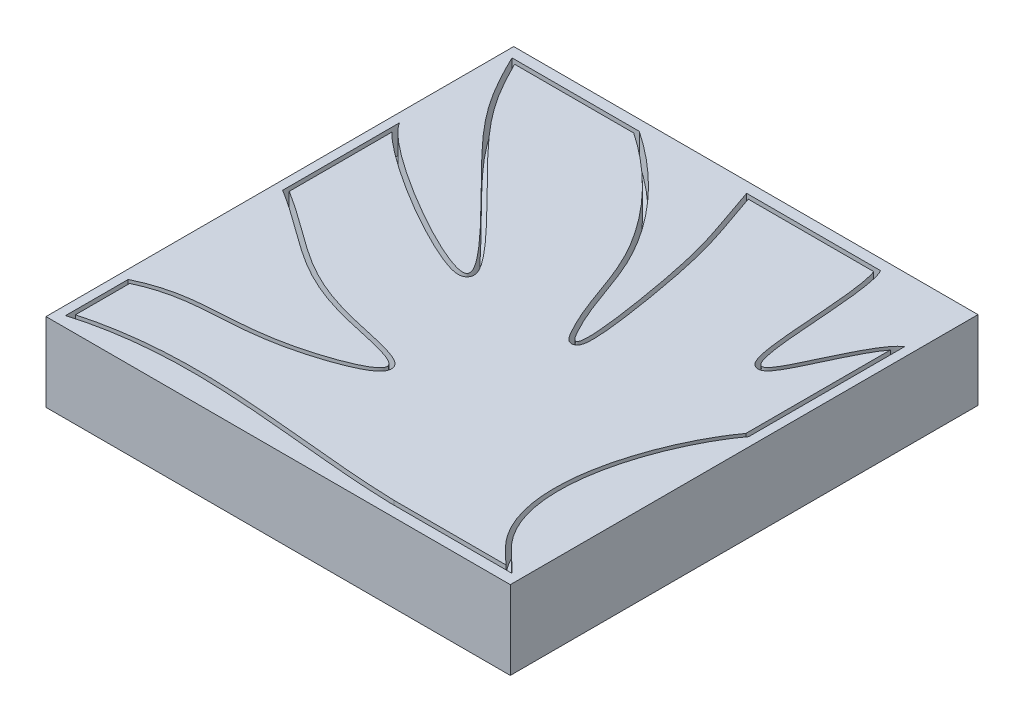
SolidWorks part; units mm, degrees
ref_plane "前视基准面" through (0, 0, 0) normal (0, 0, 1) x (1, 0, 0)
ref_plane "上视基准面" through (0, 0, 0) normal (0, 1, 0) x (1, 0, 0)
ref_plane "右视基准面" through (0, 0, 0) normal (1, 0, 0) x (0, 0, -1)
sketch "草图1" plane through (0, 0, 0) normal (0, 1, 0) x (1, 0, 0)
  circle A0 centre (0, 0) radius 18.7
  dimension "D1" = 37.4
extrude "凸台-拉伸1" add sketch "草图1" along normal blind 10
sketch "草图2" plane through (0, 10, 0) normal (0, 1, 0) x (1, 0, 0)
  line L1 (-10.5, -10.5) -> (10.5, -10.5)
  line L2 (-10.5, -10.5) -> (-10.5, 10.5)
  line L3 (-10.5, 10.5) -> (10.5, 10.5)
  line L4 (10.5, -10.5) -> (10.5, 10.5)
  line L5 (-10.5, -10.5) -> (10.5, 10.5) construction
  line L6 (-10.5, 10.5) -> (10.5, -10.5) construction
  point P0 (0, 0)
  dimension "D1" = 21
  dimension "D2" = 21
extrude "切除-拉伸1" cut sketch "草图2" against normal blind 3
sketch "草图3" plane through (0, 0, 0) normal (0, -1, 0) x (1, 0, 0)
  line L1 (-25, -25) -> (25, -25)
  line L2 (-25, -25) -> (-25, 25)
  line L3 (-25, 25) -> (25, 25)
  line L4 (25, -25) -> (25, 25)
  line L5 (-25, -25) -> (25, 25) construction
  line L6 (-25, 25) -> (25, -25) construction
  circle A0 centre (0, 0) radius 20
  point P0 (0, 0)
  circle M3 centre (0, 0) radius 18.7
  dimension "D3" = 40
  dimension "D1" = 50
  dimension "D2" = 50
extrude "凸台-拉伸2" add sketch "草图3" against normal blind 10 separate body
extrude "凸台-拉伸3" add sketch "草图3<2>" against normal blind 2.75 contours A0 M3 region at (-19.4343, 0, 0)
sketch "草图3<2>" plane through (0, 0, 0) normal (0, -1, 0) x (1, 0, 0) same geometry as "草图3"
sketch "草图4" plane through (0, 7, 0) normal (0, 1, 0) x (1, 0, 0)
  line L0 (-10.5, 10.5) -> (10.5, 10.5) construction
  line L1 (-10.5, 10.5) -> (-10.5, -10.5) construction
  line L2 (-7, -2.5) -> (-5, -2.5)
  line L3 (-7, -2.5) -> (-7, 10.5)
  line L4 (-7, 10.5) -> (-5, 10.5)
  line L5 (-5, -2.5) -> (-5, 10.5)
  line L6 (-7, -2.5) -> (-5, 10.5) construction
  line L7 (-7, 10.5) -> (-5, -2.5) construction
  line L8 (0, 0) -> (0, 15.9153) construction
  line L9 (10.5, -10.5) -> (10.5, 10.5) construction
  line L10 (5, -2.5) -> (7, -2.5)
  line L16 (-1, -6.5) -> (1, -6.5)
  line L17 (-1, -6.5) -> (-1, 2.5)
  line L18 (-1, 2.5) -> (1, 2.5)
  line L19 (1, -6.5) -> (1, 2.5)
  line L20 (-1, -6.5) -> (1, 2.5) construction
  line L21 (-1, 2.5) -> (1, -6.5) construction
  line L23 (-10.5, -10.5) -> (10.5, -10.5) construction
  line L24 (-10.5, -10.5) -> (10.5, -10.5) construction
  line L25 (5, -2.5) -> (5, 6.5)
  line L26 (5, 6.5) -> (7, 6.5)
  line L27 (7, -2.5) -> (7, 6.5)
  line L28 (5, -2.5) -> (7, 6.5) construction
  line L29 (5, 6.5) -> (7, -2.5) construction
  circle A0 centre (6, -9) radius 1
  point P4 (-6, 4)
  point P15 (6, 2)
  point P19 (0, -2)
  point P32 (6, 6.5)
  dimension "D7" = 2
  dimension "D1" = 3.5
  dimension "D2" = 2
  dimension "D3" = 13
  dimension "D4" = 2
  dimension "D5" = 9
  dimension "D6" = 4
  dimension "D8" = 1.5
  dimension "D9" = 2
  dimension "D10" = 3.5
  dimension "D11" = 9
  dimension "D12" = 4
extrude "凸台-拉伸4" add sketch "草图4" along normal up to surface (3 mm away) up to face at (0, 10, 0)
fillet "圆角1" radius 1 10 edges at (7, 8.5, 2.5) (5, 8.5, 2.5) (7, 8.5, -6.5) (5, 8.5, -6.5) (1, 8.5, 6.5) (-1, 8.5, 6.5) (1, 8.5, -2.5) (-1, 8.5, -2.5) (-5, 8.5, 2.5) (-7, 8.5, 2.5)
sketch "草图6" plane through (0, 10, 0) normal (0, 1, 0) x (1, 0, 0)
  circle A0 centre (0, 0) radius 18.7
extrude "切除-拉伸2" cut sketch "草图6" against normal blind 1.1
sketch "草图7" plane through (0, 8.9, 0) normal (0, 1, 0) x (1, 0, 0)
  line L1 (-10.5, -10.5) -> (10.5, -10.5)
  line L2 (-10.5, -10.5) -> (-10.5, 10.5)
  line L3 (-10.5, 10.5) -> (10.5, 10.5)
  line L4 (10.5, -10.5) -> (10.5, 10.5)
  line L5 (-10.5, -10.5) -> (10.5, 10.5) construction
  line L6 (-10.5, 10.5) -> (10.5, -10.5) construction
  point P0 (0, 0)
extrude "切除-拉伸3" cut sketch "草图7" against normal up to surface (1.9 mm away) contours L2 L1 L4 L3 up to face at (6, 7, 8)
sketch "草图8" plane through (0, 7, 0) normal (0, 1, 0) x (1, 0, 0)
  line L0 (-10.5, -10.5) -> (-10.5, -7.5542)
  line L5 (-10.5, -10.5) -> (10.5, -10.5)
  line L6 (-10.5, -10.5) -> (-10.5, 10.5)
  line L7 (-10.5, 10.5) -> (10.5, 10.5)
  line L8 (10.5, -10.5) -> (10.5, 10.5)
  line L9 (-10.5, -10.5) -> (10.5, 10.5) construction
  line L10 (-10.5, 10.5) -> (10.5, -10.5) construction
  line L11 (-10.5, 10.5) -> (10.5, 10.5) construction
  line L12 (-10.5, -10.5) -> (-10.5, 10.5) construction
  line L14 (10.5, -10.5) -> (10.5, 10.5) construction
  line L15 (10.5, 10.5) -> (10.5, -10.5) construction
  spline S0 degree 3 poles (10.5, -10.5) (10.0836, -10.0603) (6.774, -7.4821) (8.8307, -1.5924) (10.5, 0.633) knots 0 0 0 0 0.150773 1 1 1 1
  spline S1 degree 3 poles (-10.5, -10.5) (-5.5602, -9.0408) (-0.3039, -10.3532) (4.7427, -10.5) knots 0 0 0 0 1 1 1 1
  spline S2 degree 3 poles (-10.5, -7.5542) (-8.2032, -6.4464) (-5.9312, -7.3234) (0.8444, -4.8084) (-6.6087, -3.7535) (-8.0088, -1.8158) (-10.5, -0.29) knots 0 0 0 0 0.323774 0.482802 0.639495 1 1 1 1
  spline S3 degree 3 poles (-10.5, 5.5901) (-11.4168, 4.864) (2.0004, -3.0744) (-7.971, 6.3127) (-9.4742, 8.3819) (-10.5, 10.5) knots 0 0 0 0 0.424237 0.730172 1 1 1 1
  spline S4 degree 3 poles (6.837, 10.5) (7.49, 9.3301) (7.0988, -0.6383) (9.5891, 7.3666) (10.5, 7.9756) knots 0 0 0 0 0.583089 1 1 1 1
  spline S5 degree 3 poles (-4.5118, 10.5) (-2.3946, 9.0758) (0.6061, 5.9399) (1.5035, 2.1027) (3.0269, -0.569) (1.8715, 7.2569) (1.3203, 8.1382) (0.5364, 10.5) knots 0 0 0 0 0.349352 0.532247 0.547438 0.729892 1 1 1 1
  point P0 (0, 0)
  line M8 (10.5, 10.5) -> (-10.5, 10.5)
  line M9 (-10.5, 10.5) -> (-10.5, -10.5)
  line M10 (-10.5, -10.5) -> (10.5, -10.5)
  line M11 (10.5, -10.5) -> (10.5, 10.5)
extrude "凸台-拉伸5" add sketch "草图8" along normal up to surface (1.9 mm away) contours L6 S2 | L6 S3 | L7 M9 | L7 S5 | M8 M11 | S0 M11 | S1 M10 | S3 L6 M9 region at (-4.1412, 7, 10.236) region at (0.417, 7, 0.226) region at (-7.1011, 7, 4.574) region at (9.5813, 7, 5.2846) region at (-7.5709, 7, -4.6995) region at (8.6461, 7, -7.9601) region at (0.0926, 7, -7.0369) up to face at (0, 8.9, 18.7)
sketch "草图14" plane through (0, 10, 0) normal (0, 1, 0) x (1, 0, 0)
  circle A0 centre (0, 0) radius 23
  circle A1 centre (0, 0) radius 18.7
  dimension "D1" = 46
extrude "切除-拉伸4" cut sketch "草图14" against normal up to surface (7.25 mm away) up to face at (0, 2.75, -18.7)
extrude "切除-拉伸5" cut sketch "草图8<4>" along normal through all contours L7 S5 S3 S2 S1 L5 S0 L8 M8 M9 region at (0.417, 7, 0.226)
sketch "草图8<4>" plane through (0, 7, 0) normal (0, 1, 0) x (1, 0, 0) same geometry as "草图8"
sketch "草图17" plane through (0, 7, 0) normal (0, 1, 0) x (1, 0, 0)
  line L12 (6.837, 10.5) -> (0.5364, 10.5)
  line L13 (-4.5118, 10.5) -> (-10.5, 10.5)
  line L14 (-10.5, 5.2084) -> (-10.5, -0.29)
  line L15 (-10.5, -7.5542) -> (-10.5, -10.5)
  line L16 (4.7427, -10.5) -> (10.5, -10.5)
  line L17 (10.5, 0.633) -> (10.5, 7.9756)
  line L18 (6.837, 10.5) -> (0.5364, 10.5)
  line L19 (-4.5118, 10.5) -> (-10.5, 10.5)
  line L20 (-10.5, 5.2084) -> (-10.5, -0.29)
  line L21 (-10.5, -7.5542) -> (-10.5, -10.5)
  line L22 (4.7427, -10.5) -> (10.5, -10.5)
  line L23 (10.5, 0.633) -> (10.5, 7.9756)
  spline S6 degree 3 poles (-262.5303, -2979.3771) (53.9529, 236.6002) (-35.384, -262.5379) (46.8562, 308.5135) (-528.3509, -2941.2583) knots -3.153585 -3.153585 -3.153585 -3.153585 0.416911 4.562861 4.562861 4.562861 4.562861 only from (10.5, 7.9756) to (6.837, 10.5)
  spline S7 degree 3 poles (10.5, 7.9756) (9.5891, 7.3666) (7.0988, -0.6383) (7.49, 9.3301) (6.837, 10.5) knots 0 0 0 0 0.416911 1 1 1 1
  spline S13 degree 3 poles (-506.1169, 2967.2579) (10.061, -151.5029) (-3.7388, 45.254) (3.0269, -0.569) (1.5035, 2.1027) (-8.0704, 43.0429) (-272.5739, 12.6073) (2473.2499, -1675.4408) knots -2.271064 -2.271064 -2.271064 -2.271064 0.270108 0.452562 0.467753 0.650648 6.293276 6.293276 6.293276 6.293276 only from (0.5364, 10.5) to (-4.5118, 10.5)
  spline S14 degree 3 poles (-1562.7747, 2577.3416) (76.8615, -50.9214) (-36.0004, 32.6999) (23.2166, -23.0475) (-265.3668, 176.7392) (2641.367, -1397.0217) knots -2.763113 -2.763113 -2.763113 -2.763113 0.317717 0.623651 3.175614 3.175614 3.175614 3.175614 only from (-10.5, 10.5) to (-10.5, 5.2084)
  spline S15 degree 3 poles (-3004.25, -183.9965) (141.0837, 66.096) (-42.0808, 1.2669) (0.8444, -4.8084) (-36.3707, -18.6218) (65.4374, 102.2765) (-1687.7365, -2494.6858) knots -3.218418 -3.218418 -3.218418 -3.218418 0.360505 0.517198 0.676226 3.872947 3.872947 3.872947 3.872947 only from (-10.5, -0.29) to (-10.5, -7.5542)
  spline S16 degree 3 poles (247.3621, -2997.8169) (-443.0693, 2994.6119) (452.3422, -3014.0913) (-273.5872, 2974.9476) knots -8.430917 -8.430917 -8.430917 -8.430917 9.836231 9.836231 9.836231 9.836231 only from (-10.5, -10.5) to (4.7427, -10.5)
  spline S17 degree 3 poles (-2520.6962, -1620.1192) (96.3772, 11.3954) (-137.8299, -83.4235) (248.9298, 204.9384) (-1589.491, -2535.7251) knots -3.440476 -3.440476 -3.440476 -3.440476 0.150773 7.316653 7.316653 7.316653 7.316653 only from (10.5, -10.5) to (10.5, 0.633)
  spline S19 degree 3 poles (0.5364, 10.5) (1.3203, 8.1382) (1.8715, 7.2569) (3.0269, -0.569) (1.5035, 2.1027) (0.6061, 5.9399) (-2.3946, 9.0758) (-4.5118, 10.5) knots 0 0 0 0 0.270108 0.452562 0.467753 0.650648 1 1 1 1
  spline S20 degree 3 poles (-10.5, 10.5) (-9.4742, 8.3819) (-7.971, 6.3127) (1.5228, -2.6248) (-9.7459, 3.8864) (-10.5, 5.2084) knots 0.047888 0.047888 0.047888 0.047888 0.317717 0.623651 1 1 1 1
  spline S21 degree 3 poles (-10.5, -0.29) (-8.0088, -1.8158) (-6.6087, -3.7535) (0.8444, -4.8084) (-5.9312, -7.3234) (-8.2032, -6.4464) (-10.5, -7.5542) knots 0 0 0 0 0.360505 0.517198 0.676226 1 1 1 1
  spline S22 degree 3 poles (-10.5, -10.5) (-5.5602, -9.0408) (-0.3039, -10.3532) (4.7427, -10.5) knots 0 0 0 0 1 1 1 1
  spline S23 degree 3 poles (10.5, -10.5) (10.0836, -10.0603) (6.774, -7.4821) (8.8307, -1.5924) (10.5, 0.633) knots 0 0 0 0 0.150773 1 1 1 1
  dimension "D1" = 0
extrude "凸台-拉伸6" add sketch "草图17" along normal blind 0.7
sketch "草图18" plane through (0, 7.7, 0) normal (0, 1, 0) x (1, 0, 0)
  line L6 (4.7427, -10.5) -> (10.5, -10.5)
  line L7 (10.5, 0.633) -> (10.5, 7.9756)
  line L8 (6.837, 10.5) -> (0.5364, 10.5)
  line L9 (-4.5118, 10.5) -> (-10.5, 10.5)
  line L10 (-10.5, 5.2084) -> (-10.5, -0.29)
  line L11 (-10.5, -7.5542) -> (-10.5, -10.5)
  line L12 (4.7427, -10.5) -> (10.5, -10.5)
  line L13 (10.5, 0.633) -> (10.5, 7.9756)
  line L14 (6.837, 10.5) -> (0.5364, 10.5)
  line L15 (-4.5118, 10.5) -> (-10.5, 10.5)
  line L16 (-10.5, 5.2084) -> (-10.5, -0.29)
  line L17 (-10.5, -7.5542) -> (-10.5, -10.5)
  spline S6 degree 3 poles (247.3621, -2997.8169) (-443.0693, 2994.6119) (452.3422, -3014.0913) (-273.5872, 2974.9476) knots -8.430917 -8.430917 -8.430917 -8.430917 9.836231 9.836231 9.836231 9.836231 only from (-10.5, -10.5) to (4.7427, -10.5)
  spline S7 degree 3 poles (-2520.6962, -1620.1192) (96.3772, 11.3954) (-137.8299, -83.4235) (248.9298, 204.9384) (-1589.491, -2535.7251) knots -3.440476 -3.440476 -3.440476 -3.440476 0.150773 7.316653 7.316653 7.316653 7.316653 only from (10.5, -10.5) to (10.5, 0.633)
  spline S8 degree 3 poles (-262.5303, -2979.3771) (53.9529, 236.6002) (-35.384, -262.5379) (46.8562, 308.5135) (-528.3509, -2941.2583) knots -3.153585 -3.153585 -3.153585 -3.153585 0.416911 4.562861 4.562861 4.562861 4.562861 only from (10.5, 7.9756) to (6.837, 10.5)
  spline S9 degree 3 poles (-506.1169, 2967.2579) (10.061, -151.5029) (-3.7388, 45.254) (3.0269, -0.569) (1.5035, 2.1027) (-8.0704, 43.0429) (-272.5739, 12.6073) (2473.2499, -1675.4408) knots -2.271064 -2.271064 -2.271064 -2.271064 0.270108 0.452562 0.467753 0.650648 6.293276 6.293276 6.293276 6.293276 only from (0.5364, 10.5) to (-4.5118, 10.5)
  spline S10 degree 3 poles (-1562.7747, 2577.3416) (76.8615, -50.9214) (-36.0004, 32.6999) (23.2166, -23.0475) (-265.3668, 176.7392) (2641.367, -1397.0217) knots -2.811002 -2.811002 -2.811002 -2.811002 0.269828 0.575763 3.127726 3.127726 3.127726 3.127726 only from (-10.5, 10.5) to (-10.5, 5.2084)
  spline S11 degree 3 poles (-3004.25, -183.9965) (141.0837, 66.096) (-42.0808, 1.2669) (0.8444, -4.8084) (-36.3707, -18.6218) (65.4374, 102.2765) (-1687.7365, -2494.6858) knots -3.218418 -3.218418 -3.218418 -3.218418 0.360505 0.517198 0.676226 3.872947 3.872947 3.872947 3.872947 only from (-10.5, -0.29) to (-10.5, -7.5542)
  spline S12 degree 3 poles (-10.5, -10.5) (-5.5602, -9.0408) (-0.3039, -10.3532) (4.7427, -10.5) knots 0 0 0 0 1 1 1 1
  spline S13 degree 3 poles (10.5, -10.5) (10.0836, -10.0603) (6.774, -7.4821) (8.8307, -1.5924) (10.5, 0.633) knots 0 0 0 0 0.150773 1 1 1 1
  spline S14 degree 3 poles (10.5, 7.9756) (9.5891, 7.3666) (7.0988, -0.6383) (7.49, 9.3301) (6.837, 10.5) knots 0 0 0 0 0.416911 1 1 1 1
  spline S15 degree 3 poles (0.5364, 10.5) (1.3203, 8.1382) (1.8715, 7.2569) (3.0269, -0.569) (1.5035, 2.1027) (0.6061, 5.9399) (-2.3946, 9.0758) (-4.5118, 10.5) knots 0 0 0 0 0.270108 0.452562 0.467753 0.650648 1 1 1 1
  spline S16 degree 3 poles (-10.5, 10.5) (-9.4742, 8.3819) (-7.971, 6.3127) (1.5228, -2.6248) (-9.7459, 3.8864) (-10.5, 5.2084) knots 0 0 0 0 0.269828 0.575763 0.952112 0.952112 0.952112 0.952112
  spline S17 degree 3 poles (-10.5, -0.29) (-8.0088, -1.8158) (-6.6087, -3.7535) (0.8444, -4.8084) (-5.9312, -7.3234) (-8.2032, -6.4464) (-10.5, -7.5542) knots 0 0 0 0 0.360505 0.517198 0.676226 1 1 1 1
  dimension "D1" = 0
extrude "切除-拉伸6" cut sketch "草图18" against normal blind 0.3
sketch "草图21" plane through (0, 8.9, 0) normal (0, 1, 0) x (1, 0, 0)
  circle A0 centre (0, 0) radius 16
  dimension "D1" = 32
extrude "切除-拉伸7" cut sketch "草图21" against normal blind 0.2
sketch "草图24" plane through (0, 8.9, 0) normal (0, 1, 0) x (1, 0, 0)
  circle A0 centre (0, 0) radius 15.5
  circle A1 centre (0, 0) radius 16
  dimension "D1" = 31
extrude "切除-拉伸9" cut sketch "草图24" against normal blind 0.5
sketch "草图25" plane through (0, 8.7, 0) normal (0, 1, 0) x (1, 0, 0)
  line L1 (-10.9202, -11) -> (10.9202, -11)
  line L2 (-10.9202, -11) -> (-10.9202, 11)
  line L3 (-10.9202, 11) -> (10.9202, 11)
  line L4 (10.9202, -11) -> (10.9202, 11)
  line L5 (-10.9202, -11) -> (10.9202, 11) construction
  line L6 (-10.9202, 11) -> (10.9202, -11) construction
  circle A0 centre (0, 0) radius 15.5 construction
  point P0 (0, 0)
  dimension "D1" = 22
extrude "切除-拉伸10" cut sketch "草图25" against normal through all both and the other way through all flip side to cut
sketch "草图26" plane through (10.9202, 0, 0) normal (1, 0, 0) x (0, 0, -1)
  line L0 (11, 0) -> (11, 8.7) construction
  line L1 (-11, 0) -> (11, 0)
  line L2 (-11, 0) -> (-11, 5)
  line L3 (-11, 5) -> (11, 5)
  line L4 (11, 0) -> (11, 5)
  dimension "D1" = 5
extrude "切除-拉伸11" cut sketch "草图26" against normal through all
sketch "草图27" plane through (0, 7.4, 0) normal (0, 1, 0) x (1, 0, 0)
  line L0 (4.7456, -10.3) -> (10.0136, -10.3)
  line L1 (10.3, 0.6992) -> (10.3, 7.4931)
  line L2 (6.7112, 10.3) -> (0.8141, 10.3)
  line L3 (-4.573, 10.3) -> (-10.1794, 10.3)
  line L4 (-10.3, 4.6461) -> (-10.3, -0.1784)
  line L5 (-10.3, -7.6809) -> (-10.3, -10.2349)
  line L6 (4.7427, -10.5) -> (10.5, -10.5)
  line L7 (10.5, 0.633) -> (10.5, 7.9756)
  line L8 (6.837, 10.5) -> (0.5364, 10.5)
  line L9 (-4.5118, 10.5) -> (-10.5, 10.5)
  line L10 (-10.5, 5.2084) -> (-10.5, -0.29)
  line L11 (-10.5, -7.5542) -> (-10.5, -10.5)
  line L12 (4.7427, -10.5) -> (10.5, -10.5)
  line L13 (10.5, 0.633) -> (10.5, 7.9756)
  line L14 (6.837, 10.5) -> (0.5364, 10.5)
  line L15 (-4.5118, 10.5) -> (-10.5, 10.5)
  line L16 (-10.5, 5.2084) -> (-10.5, -0.29)
  line L17 (-10.5, -7.5542) -> (-10.5, -10.5)
  spline S0 degree 1 poles (10.0136, -10.3) (10.3, 0.6992) knots 0 0 1 1 construction
  spline S1 degree 1 poles (10.3, 7.4931) (6.7112, 10.3) knots 0 0 1 1 construction
  spline S2 degree 1 poles (0.8141, 10.3) (-4.573, 10.3) knots 0 0 1 1 construction
  spline S3 degree 1 poles (-10.1794, 10.3) (-10.3, 4.6461) knots 0 0 1 1 construction
  spline S4 degree 1 poles (-10.3, -0.1784) (-10.3, -7.6809) knots 0 0 1 1 construction
  spline S5 degree 1 poles (-10.3, -10.2349) (4.7456, -10.3) knots 0 0 1 1 construction
  spline S6 degree 3 poles (481.745, -4983.9622) (-715.6022, 4983.6308) (728.4385, -5002.6644) (-518.6742, 4959.757) knots -10.117878 -10.117878 -10.117878 -10.117878 11.522967 11.522967 11.522967 11.522967 only from (-10.5, -10.5) to (4.7427, -10.5)
  spline S7 degree 3 poles (-4218.4185, -2676.7243) (126.8731, 24.2206) (-191.7156, -114.0779) (343.8418, 274.6927) (-2712.0887, -4190.7372) knots -4.088984 -4.088984 -4.088984 -4.088984 0.150773 8.527206 8.527206 8.527206 8.527206 only from (10.5, -10.5) to (10.5, 0.633)
  spline S8 degree 3 poles (-460.2102, -4969.5423) (69.3026, 323.0716) (-51.2945, -361.1418) (63.1927, 420.9514) (-875.9776, -4910.566) knots -3.769318 -3.769318 -3.769318 -3.769318 0.416911 5.263004 5.263004 5.263004 5.263004 only from (10.5, 7.9756) to (6.837, 10.5)
  spline S9 degree 3 poles (-830.8792, 4940.4531) (15.1478, -222.6713) (-4.8438, 52.7384) (3.0269, -0.569) (1.5035, 2.1027) (-9.6711, 49.8876) (-368.4114, 0.4014) (4185.3157, -2709.0887) knots -2.718399 -2.718399 -2.718399 -2.718399 0.270108 0.452562 0.467753 0.650648 7.269769 7.269769 7.269769 7.269769 only from (0.5364, 10.5) to (-4.5118, 10.5)
  spline S10 degree 3 poles (-2625.567, 4271.2999) (117.6519, -81.3244) (-41.5175, 37.8937) (27.5081, -27.0876) (-359.4761, 242.0522) (4398.4167, -2352.036) knots -3.364301 -3.364301 -3.364301 -3.364301 0.269828 0.575763 3.55811 3.55811 3.55811 3.55811 only from (-10.5, 10.5) to (-10.5, 5.2084)
  spline S11 degree 3 poles (-4997.3721, -347.4381) (209.3771, 89.6854) (-49.0367, 2.2514) (0.8444, -4.8084) (-42.3872, -20.855) (103.8264, 147.0328) (-2808.2355, -4151.2621) knots -3.849538 -3.849538 -3.849538 -3.849538 0.360505 0.517198 0.676226 4.440802 4.440802 4.440802 4.440802 only from (-10.5, -0.29) to (-10.5, -7.5542)
  spline S12 degree 3 poles (-10.5, -10.5) (-5.5602, -9.0408) (-0.3039, -10.3532) (4.7427, -10.5) knots 0 0 0 0 1 1 1 1
  spline S13 degree 3 poles (10.5, -10.5) (10.0836, -10.0603) (6.774, -7.4821) (8.8307, -1.5924) (10.5, 0.633) knots 0 0 0 0 0.150773 1 1 1 1
  spline S14 degree 3 poles (10.5, 7.9756) (9.5891, 7.3666) (7.0988, -0.6383) (7.49, 9.3301) (6.837, 10.5) knots 0 0 0 0 0.416911 1 1 1 1
  spline S15 degree 3 poles (0.5364, 10.5) (1.3203, 8.1382) (1.8715, 7.2569) (3.0269, -0.569) (1.5035, 2.1027) (0.6061, 5.9399) (-2.3946, 9.0758) (-4.5118, 10.5) knots 0 0 0 0 0.270108 0.452562 0.467753 0.650648 1 1 1 1
  spline S16 degree 3 poles (-10.5, 10.5) (-9.4742, 8.3819) (-7.971, 6.3127) (1.5228, -2.6248) (-9.7459, 3.8864) (-10.5, 5.2084) knots 0 0 0 0 0.269828 0.575763 0.952112 0.952112 0.952112 0.952112
  spline S17 degree 3 poles (-10.5, -0.29) (-8.0088, -1.8158) (-6.6087, -3.7535) (0.8444, -4.8084) (-5.9312, -7.3234) (-8.2032, -6.4464) (-10.5, -7.5542) knots 0 0 0 0 0.360505 0.517198 0.676226 1 1 1 1
  spline S18 degree 3 poles (10.0136, -10.3) (9.6568, -9.9629) (8.909, -9.3055) (8.2381, -7.9702) (7.9853, -6.475) (8.0611, -4.8848) (8.3969, -3.2865) (8.9256, -1.7584) (9.4695, -0.6168) (9.9424, 0.1866) (10.1739, 0.5279) (10.3, 0.6992) knots 0.040456 0.040456 0.040456 0.040456 0.159574 0.278691 0.397809 0.516926 0.636044 0.755162 0.874279 0.933838 0.993397 0.993397 0.993397 0.993397
  spline S19 degree 3 poles (10.3, 7.4931) (10.2341, 7.4071) (10.1176, 7.2378) (9.8604, 6.8079) (9.5434, 6.188) (9.1721, 5.394) (8.8228, 4.6491) (8.5592, 4.145) (8.3559, 3.8478) (8.2098, 3.6836) (7.9684, 3.5654) (7.705, 3.6845) (7.5949, 3.8665) (7.4788, 4.1591) (7.3775, 4.6551) (7.2836, 5.4258) (7.2084, 6.3159) (7.1393, 7.2643) (7.0657, 8.2074) (6.9762, 9.0829) (6.882, 9.695) (6.7863, 10.0904) (6.7414, 10.2269) (6.7112, 10.3) knots 0.053955 0.053955 0.053955 0.053955 0.082947 0.111938 0.169922 0.227905 0.285888 0.343872 0.372863 0.401855 0.430847 0.459838 0.48883 0.517822 0.575805 0.633788 0.691772 0.749755 0.807738 0.865722 0.923705 0.952697 0.981688 0.981688 0.981688 0.981688
  spline S20 degree 3 poles (0.8141, 10.3) (0.893, 10.0656) (1.062, 9.5742) (1.3403, 8.7829) (1.6436, 7.9033) (1.9657, 6.7686) (2.2367, 5.5158) (2.4838, 4.1549) (2.6684, 3.0175) (2.8142, 1.9272) (2.8757, 1.1746) (2.8714, 0.7275) (2.8378, 0.5184) (2.776, 0.3627) (2.6132, 0.2338) (2.4078, 0.2746) (2.3083, 0.3621) (2.2168, 0.4685) (2.0941, 0.6589) (1.8769, 1.056) (1.6155, 1.6018) (1.3478, 2.2587) (1.0308, 3.1196) (0.6638, 4.1673) (0.1035, 5.3631) (-0.8648, 6.8929) (-2.4046, 8.6482) (-3.8198, 9.7891) (-4.573, 10.3) knots 0.010357 0.010357 0.010357 0.010357 0.041196 0.072034 0.133711 0.195388 0.257065 0.287904 0.318743 0.349581 0.38042 0.395839 0.411258 0.418968 0.426677 0.434387 0.442097 0.449806 0.457516 0.472935 0.503774 0.534612 0.565451 0.627128 0.688805 0.750482 0.873836 0.997191 0.997191 0.997191 0.997191
  spline S21 degree 3 poles (-10.1794, 10.3) (-10.0803, 10.1001) (-9.8712, 9.6898) (-9.4837, 8.9825) (-8.7993, 7.8844) (-7.8941, 6.7858) (-6.5385, 5.377) (-5.3329, 4.1633) (-4.1505, 2.9534) (-3.3293, 2.0533) (-2.8596, 1.4589) (-2.6592, 1.1495) (-2.5643, 0.9287) (-2.5267, 0.766) (-2.5686, 0.5552) (-2.7583, 0.4201) (-2.9333, 0.4054) (-3.1796, 0.4283) (-3.7034, 0.5748) (-4.7449, 1.0247) (-6.2783, 1.8386) (-7.61, 2.6398) (-8.5996, 3.2943) (-9.2732, 3.7734) (-9.8652, 4.2398) (-10.1538, 4.4985) (-10.3, 4.6461) knots 0.012573 0.012573 0.012573 0.012573 0.040843 0.069112 0.125651 0.23873 0.295269 0.351808 0.408347 0.464886 0.493156 0.521425 0.53556 0.549695 0.56383 0.577965 0.592099 0.606234 0.634504 0.691043 0.747582 0.804121 0.832391 0.86066 0.88893 0.9172 0.9172 0.9172 0.9172
  spline S22 degree 3 poles (-10.3, -0.1784) (-10.0955, -0.3052) (-9.6806, -0.5734) (-8.9503, -1.0781) (-8.1262, -1.6849) (-7.1937, -2.3482) (-6.2004, -2.9405) (-5.0426, -3.4575) (-3.8164, -3.8137) (-2.6861, -4.0614) (-1.8871, -4.2459) (-1.3328, -4.4081) (-0.9916, -4.5613) (-0.7915, -4.6927) (-0.6347, -4.9181) (-0.689, -5.2093) (-0.8481, -5.3884) (-1.1323, -5.6092) (-1.6326, -5.8669) (-2.6525, -6.2624) (-4.1152, -6.6671) (-6.0467, -6.951) (-7.5992, -6.9703) (-8.9041, -7.1832) (-9.6748, -7.4147) (-10.0988, -7.5878) (-10.3, -7.6809) knots 0.004598 0.004598 0.004598 0.004598 0.035533 0.066469 0.128339 0.190209 0.252079 0.313949 0.375819 0.406754 0.437689 0.468624 0.484091 0.499559 0.515026 0.530494 0.545961 0.561429 0.592364 0.623299 0.685169 0.747039 0.870779 0.932649 0.963584 0.994519 0.994519 0.994519 0.994519
  spline S23 degree 3 poles (-10.3, -10.2349) (-9.0841, -9.8995) (-6.5601, -9.5446) (-2.7797, -9.6609) (1.0244, -10.052) (3.4975, -10.2636) (4.7456, -10.3) knots 0.017066 0.017066 0.017066 0.017066 0.262752 0.508437 0.754122 0.999807 0.999807 0.999807 0.999807
  dimension "D1" = 0
  dimension "D2" = 0.2
extrude "凸台-拉伸7" add sketch "草图27" along normal up to surface (1.3 mm away) separate body contours L5 S23 L0 S18 L1 S19 L2 S20 L3 S21 L4 S22 region at (0.4938, 7.4, 0.2869) up to face at (-2.1144, 8.7, -0.4909)
